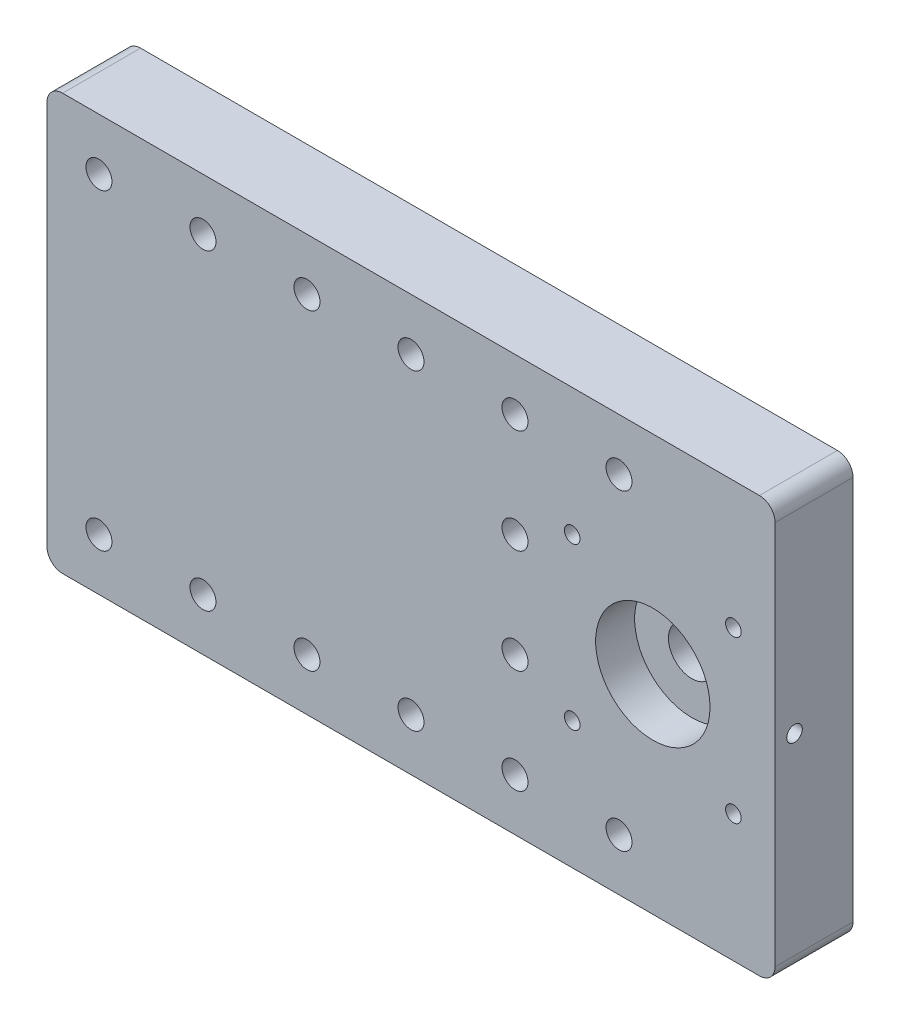
SolidWorks part; units mm, degrees
ref_plane "Płaszczyzna przednia" through (0, 0, 0) normal (0, 0, 1) x (1, 0, 0)
ref_plane "Płaszczyzna górna" through (0, 0, 0) normal (0, 1, 0) x (1, 0, 0)
ref_plane "Płaszczyzna prawa" through (0, 0, 0) normal (1, 0, 0) x (0, 0, -1)
sketch "Sketch1" plane through (0, 0, 0) normal (0, 0, 1) x (1, 0, 0)
  line L0 (0, 40) -> (71.9546, 40) construction
  line L1 (0, 0) -> (60, 0)
  line L2 (0, 0) -> (0, 80)
  line L3 (0, 80) -> (60, 80)
  line L4 (60, 0) -> (60, 80)
  line L5 (36.5, 90.7355) -> (36.5, -6.2892) construction
  line L7 (0, 80) -> (-80, 80)
  line L8 (0, 80) -> (0, 0)
  line L9 (0, 0) -> (-80, 0)
  line L10 (-80, 80) -> (-80, 0)
  circle A0 centre (10, 10) radius 2.5
  circle A1 centre (10, 30) radius 2.5
  circle A2 centre (10, 50) radius 2.5
  circle A3 centre (10, 70) radius 2.5
  circle A4 centre (30, 70) radius 2.5
  circle A5 centre (30, 10) radius 2.5
  circle A6 centre (36.5, 40) radius 11
  circle A7 centre (36.5, 40) radius 4.5
  circle A8 centre (21, 55.5) radius 1.5
  circle A9 centre (52, 55.5) radius 1.5
  circle A10 centre (52, 24.5) radius 1.5
  circle A11 centre (21, 24.5) radius 1.5
  circle A12 centre (-70, 70) radius 2.5
  circle A13 centre (-50, 70) radius 2.5
  circle A14 centre (-30, 70) radius 2.5
  circle A15 centre (-10, 70) radius 2.5
  circle A16 centre (-70, 10) radius 2.5
  circle A17 centre (-50, 10) radius 2.5
  circle A18 centre (-30, 10) radius 2.5
  circle A19 centre (-10, 10) radius 2.5
  point P50 (0, 0)
  point P51 (0, 0)
  point P52 (0, 0)
  point P53 (0, 0)
  point P54 (0, 0)
  point P55 (0, 0)
  dimension "D8" = 5
  dimension "D11" = 22
  dimension "D12" = 9
  dimension "D13" = 3
  dimension "D1" = 60
  dimension "D2" = 80
  dimension "D3" = 10
  dimension "D4" = 20
  dimension "D5" = 20
  dimension "D6" = 20
  dimension "D7" = 10
  dimension "D9" = 20
  dimension "D10" = 36.5
  dimension "D14" = 31
  dimension "D15" = 31
  dimension "D16" = 6.5
  dimension "D17" = 80
  dimension "D18" = 20
  dimension "D19" = 20
  dimension "D20" = 20
  dimension "D21" = 20
extrude "Boss-Extrude1" add sketch "Sketch1" along normal blind 15 contours L1 L4 L3 L2 A11 A10 A9 A8 A6 A5 A4 A3 A2 A1 A0 | L7 L10 L9 L2 A19 A18 A17 A16 A15 A14 A13 A12 region at (1, 40, 0) region at (-40, 40, 0)
extrude "Boss-Extrude2" add sketch "Sketch1<3>" along normal offset from surface (7.5 mm away) 7.5 contours A6 A7 region at (25.8111, 40, 0) up to face at (22.5, 24.5, 15)
sketch "Sketch1<3>" plane through (0, 0, 0) normal (0, 0, 1) x (1, 0, 0) same geometry as "Sketch1"
fillet "Fillet1" radius 3 4 edges at (60, 0, 7.5) (60, 80, 7.5) (-80, 0, 7.5) (-80, 80, 7.5)
sketch "Sketch2" plane through (60, 0, 0) normal (1, 0, 0) x (0, 0, -1)
  line L0 (-7.5, 40) -> (-15, 40) construction
  line L1 (-15, 51) -> (-15, 29) construction
  line L2 (-7.5, 51) -> (-7.5, 29) construction
  circle A0 centre (-11.25, 40) radius 1.5
  dimension "D1" = 3
extrude "Cut-Extrude1" cut sketch "Sketch2" against normal up to next
